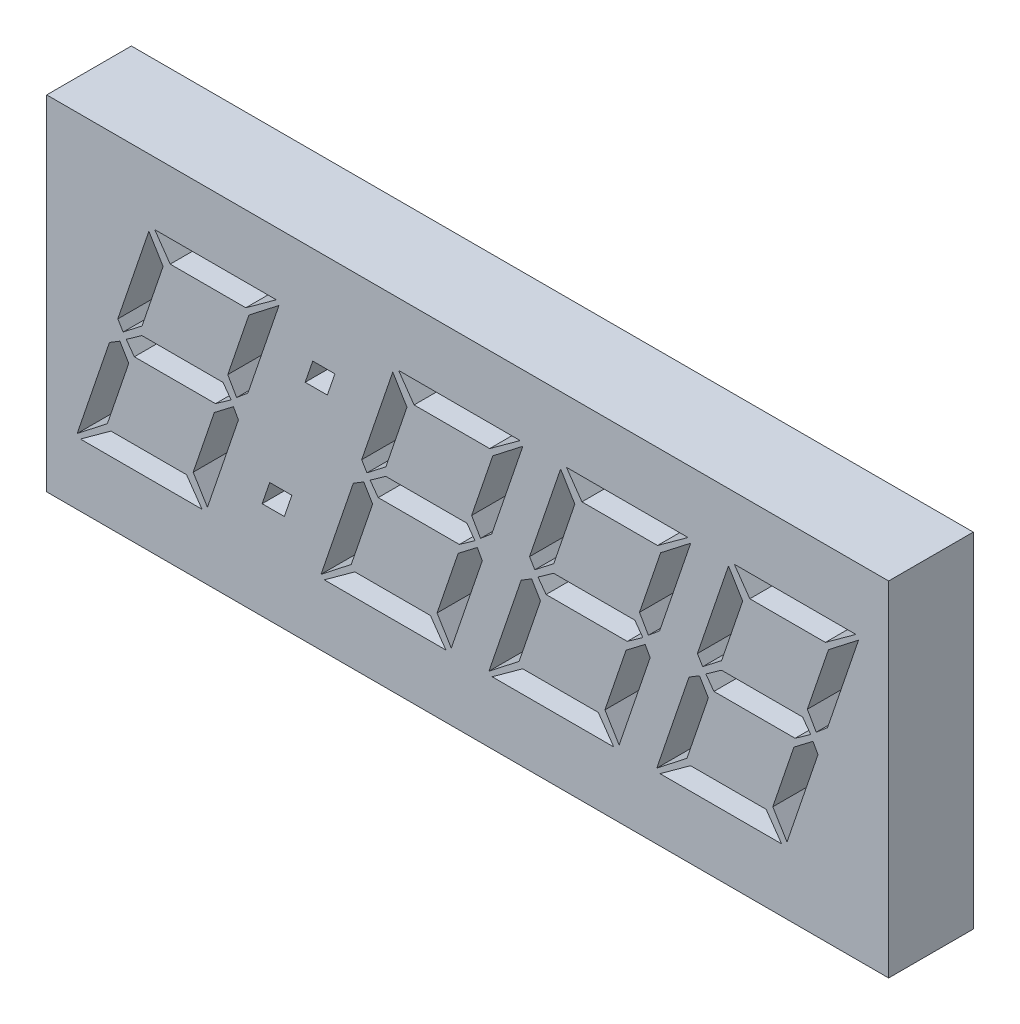
SolidWorks part; units mm, degrees
ref_plane "Спереди" through (0, 0, 0) normal (0, 0, 1) x (1, 0, 0)
ref_plane "Сверху" through (0, 0, 0) normal (0, 1, 0) x (1, 0, 0)
ref_plane "Справа" through (0, 0, 0) normal (1, 0, 0) x (0, 0, -1)
sketch "Эскиз1" plane through (0, 0, 0) normal (0, 0, 1) x (1, 0, 0)
  line L9 (65.1785, -93.2379) -> (565.1785, -93.2379)
  line L10 (65.1785, -93.2379) -> (65.1785, -313.2379)
  line L11 (65.1785, -313.2379) -> (565.1785, -313.2379)
  line L12 (565.1785, -93.2379) -> (565.1785, -313.2379)
  text T0 "<i>8:888</i>" font "DS-Digital" height 130
  dimension "D1" = 500
  dimension "D2" = 220
extrude "Бобышка-Вытянуть1" add sketch "Эскиз1" along normal blind 50
sketch "Эскиз2" plane through (0, 0, 50) normal (0, 0, 1) x (1, 0, 0)
  line L0 (225.057, -151.9154) -> (238.1505, -151.9154)
  line L1 (238.1505, -151.9154) -> (233.6789, -165.009)
  line L2 (233.6789, -165.009) -> (220.5853, -165.009)
  line L3 (220.5853, -165.009) -> (225.057, -151.9154)
  line L4 (199.6439, -226.7311) -> (212.7374, -226.7311)
  line L5 (212.7374, -226.7311) -> (208.2658, -239.8246)
  line L6 (208.2658, -239.8246) -> (195.1722, -239.8246)
  line L7 (195.1722, -239.8246) -> (199.6439, -226.7311)
  line L8 (303.7058, -260.4046) -> (231.896, -260.4046) construction
  dimension "D1" = 20.58
  dimension "D2" = 13.0935
  dimension "D3" = 13.836
  dimension "D4" = 0
extrude "Вырез-Вытянуть1" cut sketch "Эскиз2" against normal blind 65
sketch "Эскиз3" plane through (0, 0, 50) normal (0, 0, 1) x (1, 0, 0)
  line L1 (183.9606, -243.9126) -> (208.9541, -243.9126)
  line L2 (183.9606, -243.9126) -> (183.9606, -268.6669)
  line L3 (183.9606, -268.6669) -> (208.9541, -268.6669)
  line L4 (208.9541, -243.9126) -> (208.9541, -268.6669)
extrude "Бобышка-Вытянуть2" add sketch "Эскиз3" against normal blind 50
sketch "Эскиз4" plane through (0, 0, 50) normal (0, 0, 1) x (1, 0, 0)
  line L0 (131.7364, -131.3399) -> (203.5462, -131.3399) construction
  line L1 (67.9383, -94.3399) -> (565.4266, -94.3399)
  line L2 (67.9383, -94.3399) -> (67.9383, -297.4046)
  line L3 (67.9383, -297.4046) -> (565.4266, -297.4046)
  line L4 (565.4266, -94.3399) -> (565.4266, -297.4046)
  line L5 (159.6771, -260.4046) -> (87.8673, -260.4046) construction
  point P6 (0, 0)
  dimension "D1" = 37
  dimension "D2" = 37
  dimension "D3" = 18
  dimension "D4" = 18
extrude "Вырез-Вытянуть-Тонкостенный1" cut sketch "Эскиз4" against normal blind 84 thin thin type one direction wall 30
